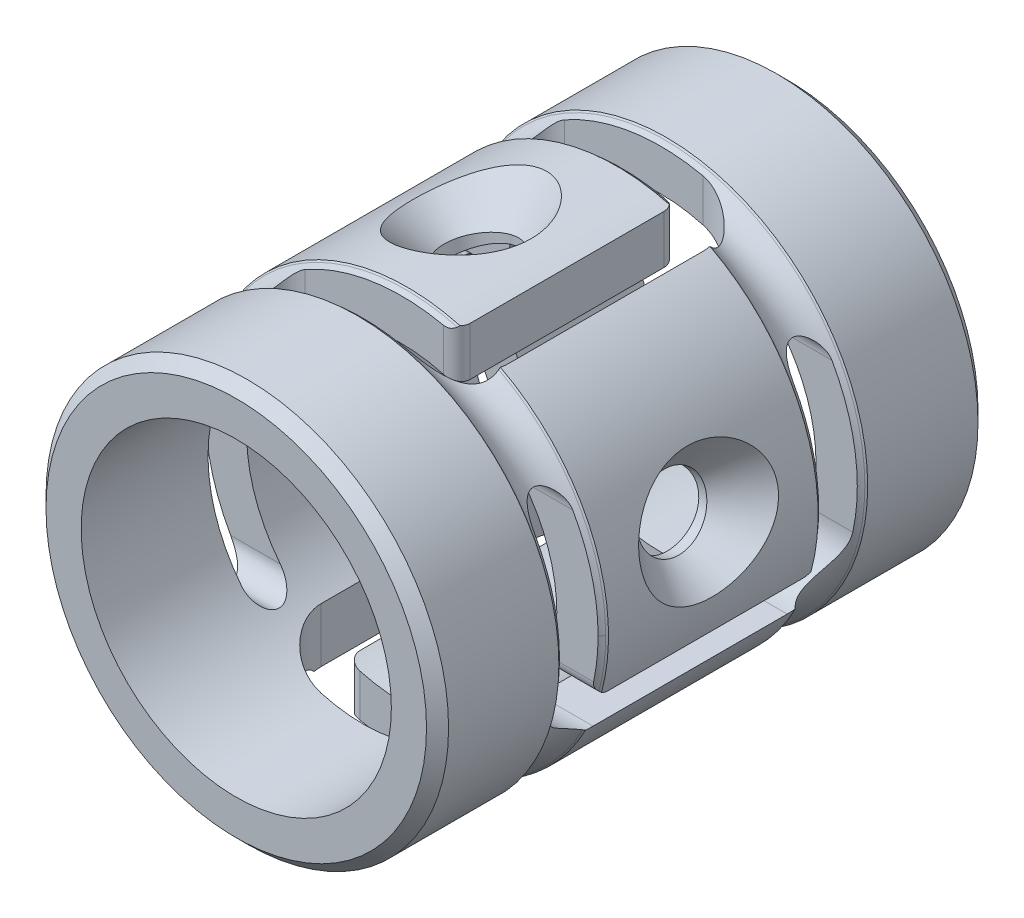
SolidWorks part; units mm, degrees
ref_plane "Front Plane" through (0, 0, 0) normal (0, 0, 1) x (1, 0, 0)
ref_plane "Top Plane" through (0, 0, 0) normal (0, 1, 0) x (1, 0, 0)
ref_plane "Right Plane" through (0, 0, 0) normal (1, 0, 0) x (0, 0, -1)
ref_axis "Axis1" through (0, 0, -15.0399) along (0, 0, 1)
ref_plane "PL-04 Assy Alignment Plane" through (0, 0, 0) normal (0.9659, -0.2588, 0) x (0, 0, -1)
sketch "Sketch2" plane through (0, 0, 0) normal (0, 0, -1) x (-1, 0, 0)
  line L1 (-0.8835, 5.3813) -> (0.0052, 3.8421)
  line L2 (0.0052, 3.8421) -> (-0.3757, 2.0503)
  line L3 (-0.3757, 2.0503) -> (0.4007, 1.8852)
  line L4 (1.5993, 0) -> (2.7099, 0)
  line L5 (1.0562, 4.969) -> (-0.8835, 5.3813)
  line L6 (1.0562, 4.969) -> (0.4007, 1.8852) construction
  line L7 (0, 1.8796) -> (0, 1.2289) construction
  line L8 (0, 1.8796) -> (-1.7321, 1.8796) construction
  line L9 (-1.0781, 4.0237) -> (-0.623, 2.3249) construction
  line L10 (0.3899, 0.6754) -> (0.8075, 1.3987) construction
  line L11 (0, 1.8796) -> (2.1037, 1.8796) construction
  line L12 (0.0052, 3.8421) -> (-1.7333, 4.2116) construction
  circle A0 centre (-0.802, 2.9932) radius 0.4483
  circle A1 centre (-0.802, 2.9932) radius 0.4318 construction
  circle A2 centre (0, 0) radius 4.1656
  circle A3 centre (0, 0) radius 3.5719
  circle A4 centre (0, 0) radius 4.6355
  point P2 (0.8661, 4.0746)
  point P17 (-0.6721, 3.1621)
  dimension "D3" = 0.8636
  dimension "D7" = 3.0988
  dimension "D8" = 7.1437
  dimension "D9" = 8.3312
  dimension "D13" = 0.8966
  dimension "D14" = 27
  dimension "D4" = 9.271
  dimension "D2" = 1.5875
  dimension "D5" = 18
  dimension "D6" = 45
  dimension "D10" = 2.286
  dimension "D11" = 30
  dimension "D12" = 60
  dimension "D15" = 5.08
  dimension "D16" = 3.7592
  dimension "D17" = 42
sketch "Sketch1" plane through (0, 0, 0) normal (1, 0, 0) x (0, 0, -1)
  line L1 (6.35, 4.3815) -> (6.35, 3.5719)
  line L2 (6.35, 3.5719) -> (-6.35, 3.5719)
  line L3 (-6.35, 4.3815) -> (-6.096, 4.6355)
  line L4 (2.5014, 0) -> (8.9089, 0) construction
  line L5 (-6.096, 4.6355) -> (-3.556, 4.6355)
  line L6 (-3.556, 4.6355) -> (-3.5233, 4.6028)
  line L7 (-2.4457, 4.6028) -> (-2.413, 4.6355)
  line L8 (-2.413, 4.6355) -> (2.413, 4.6355)
  line L12 (2.413, 4.6355) -> (2.4457, 4.6028)
  line L13 (3.5233, 4.6028) -> (3.556, 4.6355)
  line L16 (3.556, 4.6355) -> (6.096, 4.6355)
  line L17 (6.096, 4.6355) -> (6.35, 4.3815)
  line L20 (-6.35, 4.3815) -> (-6.35, 3.5719)
  arc A0 (-3.5233, 4.6028) -> (-2.4457, 4.6028) centre (-2.9845, 5.1416) ccw
  arc A1 (2.4457, 4.6028) -> (3.5233, 4.6028) centre (2.9845, 5.1416) ccw
  point P7 (0, 4.1656)
  point P8 (0, 3.5719)
  point P24 (0, 4.6355)
  dimension "D9" = 0.762
  dimension "D15" = 0.8078
  dimension "D3" = 0.2559
  dimension "D1" = 6.35
  dimension "D2" = 12.7
  dimension "D7" = 45
  dimension "D11" = 4.826
  dimension "D12" = 1.143
  dimension "D13" = 0.254
revolve "Revolve1" add sketch "Sketch1" angle 360 about L4
sketch "Sketch6" plane through (0, 0, 0) normal (0, 0, 1) x (1, 0, 0)
  line L0 (-1.0562, 4.969) -> (0.8835, 5.3813)
  line L3 (-0.0052, 3.8421) -> (0.3757, 2.0503)
  line L4 (0.3757, 2.0503) -> (-0.4007, 1.8852)
  line L5 (-0.4007, 1.8852) -> (-1.0562, 4.969)
  line L6 (-1.0562, 4.969) -> (-1.8109, 8.5194) construction
  line L8 (-0.0052, 3.8421) -> (0.3757, 2.0503) construction
  line L11 (0.8835, 5.3813) -> (-0.0052, 3.8421)
revolve "Cut-Revolve2" cut sketch "Sketch6" angle 360 about L6
ref_plane "PL-05 Slot Path Plane" through (0, 1.8796, 0) normal (0, -1, 0) x (1, 0, 0)
sketch "Sketch5" plane through (0, 1.8796, 0) normal (0, -1, 0) x (1, 0, 0)
  line L0 (-2.2225, 2.54) -> (0.9652, 2.54)
  line L1 (1.27, 2.2352) -> (1.27, -2.2352)
  line L2 (-2.2225, 3.429) -> (0.9652, 3.429)
  line L3 (2.159, 2.2352) -> (2.159, -2.2352)
  line L4 (-8.889, 0) -> (-5.8791, 0) construction
  line L5 (-2.2225, -3.429) -> (0.9652, -3.429)
  line L6 (-2.2225, -2.54) -> (0.9652, -2.54)
  arc A0 (-2.2225, 2.54) -> (-2.2225, 3.429) centre (-2.2225, 2.9845) cw
  arc A1 (0.9652, 3.429) -> (2.159, 2.2352) centre (0.9652, 2.2352) cw
  arc A2 (0.9652, 2.54) -> (1.27, 2.2352) centre (0.9652, 2.2352) cw
  arc A3 (0.9652, -2.54) -> (1.27, -2.2352) centre (0.9652, -2.2352) ccw
  arc A4 (0.9652, -3.429) -> (2.159, -2.2352) centre (0.9652, -2.2352) ccw
  arc A5 (-2.2225, -2.54) -> (-2.2225, -3.429) centre (-2.2225, -2.9845) ccw
  dimension "D1" = 0.3048
  dimension "D6" = 2.667
  dimension "D2" = 0.889
  dimension "D3" = 0.889
  dimension "D4" = 5.08
  dimension "D5" = 1.27
extrude "Cut-Extrude2" cut sketch "Sketch5" against normal blind 5.08
pattern_circular "CirPattern2" count 4 over 360 about axis through (0, 0, -15.0399) along (0, 0, 1) of "Cut-Revolve2", "Cut-Extrude2"
sketch "Sketch8" plane through (0, 0, 0) normal (1, 0, 0) x (0, 0, -1)
  line L0 (-1.3335, 14.732) -> (-1.3335, 8.382)
  line L1 (-1.3335, 8.382) -> (-2.4892, 5.207)
  line L2 (-2.4892, 5.207) -> (-2.4892, 2.032)
  line L3 (-2.4892, 2.032) -> (-2.921, 2.032)
  line L4 (-2.921, 2.032) -> (-2.921, 53.086)
  line L5 (-1.3335, 14.732) -> (1.0541, 14.732)
  line L6 (1.0541, 14.732) -> (1.0541, 14.986)
  line L7 (1.0541, 14.986) -> (9.779, 14.986)
  line L8 (10.795, 16.002) -> (10.795, 33.02)
  line L9 (9.779, 34.036) -> (6.604, 34.036)
  line L10 (6.604, 34.036) -> (6.604, 40.386)
  line L11 (6.604, 40.386) -> (16.129, 40.386)
  line L12 (16.129, 40.386) -> (16.129, 53.086)
  line L13 (16.129, 53.086) -> (-2.921, 53.086)
  line L14 (-2.921, 53.086) -> (-2.921, 65.786) construction
  arc A0 (10.795, 33.02) -> (9.779, 34.036) centre (9.779, 33.02) ccw
  arc A1 (9.779, 14.986) -> (10.795, 16.002) centre (9.779, 16.002) ccw
  dimension "D14" = 1.016
  dimension "D1" = 0.8636
  dimension "D2" = 3.175
  dimension "D3" = 3.175
  dimension "D4" = 3.175
  dimension "D5" = 12.7
  dimension "D6" = 7.9502
  dimension "D7" = 27.432
  dimension "D8" = 19.05
  dimension "D9" = 0.254
  dimension "D10" = 19.05
  dimension "D11" = 6.35
  dimension "D12" = 12.7
  dimension "D13" = 38.1
  dimension "D15" = 2.921
  dimension "D16" = 2.032
sketch "Sketch9" plane through (0, 0, 0) normal (1, 0, 0) x (0, 0, -1)
  line L0 (-19.05, 4.3688) -> (-38.1, 4.3688)
  line L1 (-38.1, 4.3688) -> (-42.91, 12.7)
  line L2 (-42.91, 12.7) -> (-66.9636, 12.7)
  line L3 (-66.9636, 12.7) -> (-66.9636, 15.875)
  line L4 (-66.9636, 15.875) -> (-32.0193, 15.875)
  line L5 (-32.0193, 15.875) -> (-23.0139, 18.288)
  line L6 (-62.3898, 0) -> (-38.3362, 0) construction
  arc A0 (-19.05, 4.3688) -> (-23.0139, 18.288) centre (-60.8117, 0) ccw
  dimension "D3" = 3.9639
  dimension "D1" = 8.7376
  dimension "D2" = 15
  dimension "D4" = 31.75
  dimension "D5" = 43.9497
  dimension "D6" = 36.576
  dimension "D7" = 3.175
  dimension "D8" = 19.05
  dimension "D9" = 60
  dimension "D10" = 19.05
revolve "Toolholder" [suppressed] add sketch "Sketch8" angle 360 about L14
revolve "Collet" [suppressed] add sketch "Sketch9" angle 360 about L6
ref_plane "Plane1" through (0, 0, 8.89) normal (0, 0, 1) x (1, 0, 0)
mirror "Mirror2" [suppressed] about plane through (0, 0, 8.89) normal (0, 0, 1) of bodies 109
sketch "Sketch10" [suppressed] plane through (0, 0, 0) normal (1, 0, 0) x (0, 0, -1)
  line L0 (-23.0139, 18.288) -> (-23.0139, 26.0278)
  line L1 (-23.0139, 26.0278) -> (-24.0299, 27.7876)
  line L2 (-24.0299, 27.7876) -> (-54.46, 27.7876)
  line L3 (-54.46, 27.7876) -> (-54.46, 15.875)
  line L4 (-32.0193, 15.875) -> (-23.0139, 18.288)
  line L5 (-54.46, 15.875) -> (-32.0193, 15.875)
  line L6 (-87.5712, 0) -> (-75.5481, 0) construction
  dimension "D1" = 55.5752
  dimension "D2" = 60
  dimension "D3" = 1.016
revolve "Indexer" [suppressed] add sketch "Sketch10" angle 360 about L6
sketch "Sketch11" plane through (0, 0, 0) normal (0, 1, 0) x (1, 0, 0)
  line L0 (-0.9652, 3.429) -> (2.2225, 3.429) construction
  line L1 (-2.159, -2.2352) -> (-2.159, 2.2352) construction
  line L2 (-1.27, 2.2352) -> (-1.27, -2.2352) construction
  line L3 (2.2225, 2.54) -> (-0.9652, 2.54) construction
  line L4 (-0.9652, -2.54) -> (2.2225, -2.54) construction
  line L5 (2.2225, -3.429) -> (-0.9652, -3.429) construction
  line L6 (-0.9652, 3.429) -> (2.2225, 3.429)
  line L7 (-2.159, -2.2352) -> (-2.159, 2.2352)
  line L8 (-1.27, 2.2352) -> (-1.27, -2.2352)
  line L9 (2.2225, 2.54) -> (-0.9652, 2.54)
  line L10 (-0.9652, -2.54) -> (2.2225, -2.54)
  line L11 (2.2225, -3.429) -> (-0.9652, -3.429)
  arc A0 (-0.9652, 3.429) -> (-2.159, 2.2352) centre (-0.9652, 2.2352) ccw construction
  arc A1 (2.2225, 2.54) -> (2.2225, 3.429) centre (2.2225, 2.9845) ccw construction
  arc A2 (-0.9652, 2.54) -> (-1.27, 2.2352) centre (-0.9652, 2.2352) ccw construction
  arc A3 (-1.27, -2.2352) -> (-0.9652, -2.54) centre (-0.9652, -2.2352) ccw construction
  arc A4 (-2.159, -2.2352) -> (-0.9652, -3.429) centre (-0.9652, -2.2352) ccw construction
  arc A5 (2.2225, -3.429) -> (2.2225, -2.54) centre (2.2225, -2.9845) ccw construction
  arc A6 (-0.9652, 3.429) -> (-2.159, 2.2352) centre (-0.9652, 2.2352) ccw
  arc A7 (2.2225, 2.54) -> (2.2225, 3.429) centre (2.2225, 2.9845) ccw
  arc A8 (-0.9652, 2.54) -> (-1.27, 2.2352) centre (-0.9652, 2.2352) ccw
  arc A9 (-1.27, -2.2352) -> (-0.9652, -2.54) centre (-0.9652, -2.2352) ccw
  arc A10 (-2.159, -2.2352) -> (-0.9652, -3.429) centre (-0.9652, -2.2352) ccw
  arc A11 (2.2225, -3.429) -> (2.2225, -2.54) centre (2.2225, -2.9845) ccw
ref_plane "Plane2" through (-1.0562, 4.969, 0) normal (0.2079, -0.9781, 0) x (0.9781, 0.2079, 0)
